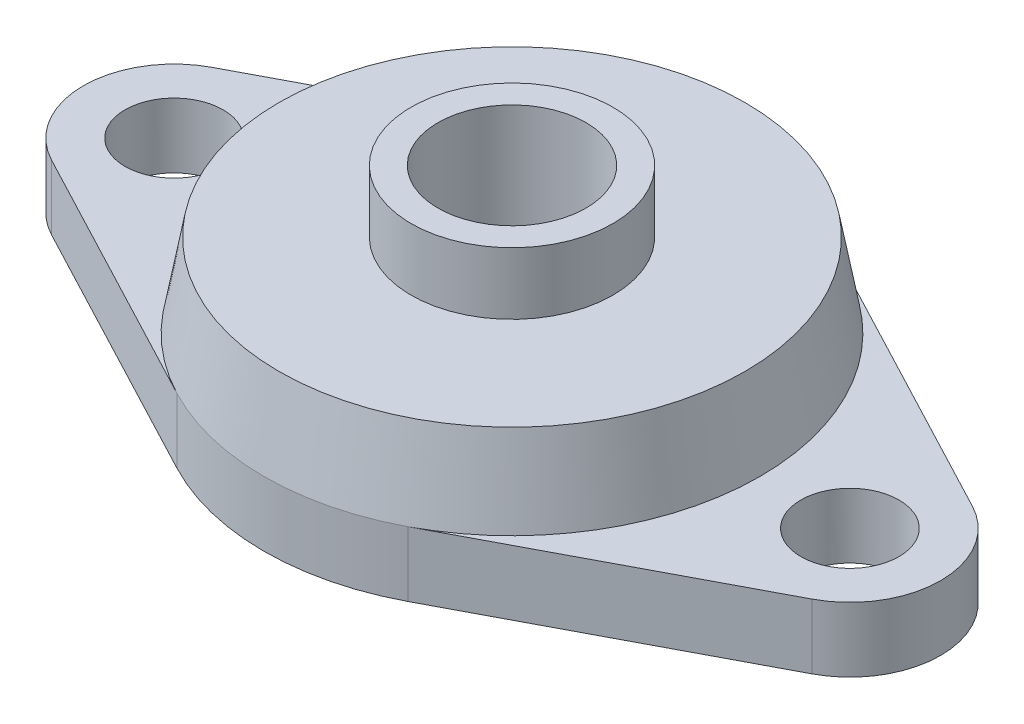
SolidWorks part; units mm, degrees
ref_plane "Front Plane" through (0, 0, 0) normal (0, 0, 1) x (1, 0, 0)
ref_plane "Top Plane" through (0, 0, 0) normal (0, 1, 0) x (1, 0, 0)
ref_plane "Right Plane" through (0, 0, 0) normal (1, 0, 0) x (0, 0, -1)
ref_axis "Axis1" through (0, -0.5675, 0) along (0, 1, 0)
imported_body "Imported1" [suppressed]
imported_body "Imported2" [suppressed]
imported_body "Imported3" [suppressed]
imported_body "Imported4" [suppressed]
sketch "Sketch1" plane through (0, 0, 0) normal (0, 1, 0) x (1, 0, 0)
  line L0 (-23.15, 0) -> (0, 0)
  line L2 (0, 0) -> (0, 13.4)
  line L3 (-23.15, 0) -> (-23.15, 8.4691) construction
  line L8 (-6.2411, 11.8579) -> (-20.5322, 4.3361)
  arc A11 (-20.5322, 4.3361) -> (-23.15, 0) centre (-18.25, 0) ccw
  arc A12 (0, 13.4) -> (-6.2411, 11.8579) centre (0, 0) ccw
  dimension "D3" = 4.9
  dimension "D2" = 23.15
  dimension "D4" = 13.4
extrude "Boss-Extrude1" add sketch "Sketch1" along normal blind 3.5 separate body
mirror "Mirror3" about plane through (0, 3.5, 0) normal (-1, 0, 0) of bodies 105
mirror "Mirror4" about plane through (-23.15, 3.5, 0) normal (0, 0, -1) of bodies 107
sketch "Sketch2" plane through (0, 0, 0) normal (0, 0, 1) x (1, 0, 0)
  line L0 (0, 0) -> (0, 11.35)
  line L2 (0, 11.35) -> (5.45, 11.35)
  line L3 (5.45, 11.35) -> (5.45, 8)
  line L4 (5.45, 8) -> (12.5825, 8)
  line L5 (12.5825, 8) -> (13.4, 3.5)
  line L6 (13.4, 3.5) -> (13.4, 0)
  line L7 (13.4, 0) -> (0, 0)
  dimension "D1" = 11.35
  dimension "D2" = 5.45
  dimension "D3" = 8
  dimension "D4" = 13.4
  dimension "D5" = 3.5
  dimension "D6" = 12.5825
revolve "Revolve1" add sketch "Sketch2" angle 360 about L0
sketch "Sketch3" plane through (0, 0, 0) normal (0, -1, 0) x (1, 0, 0)
  circle A0 centre (0, 0) radius 4
  dimension "D1" = 8
extrude "Cut-Extrude1" cut sketch "Sketch3" against normal through all
hole_wizard "M5 Clearance Hole1" positions "Sketch5" profile "Sketch4" hole size "M5" standard "ANSI Metric" end condition through all
sketch "Sketch5" plane through (0, 0, 0) normal (0, -1, 0) x (-1, 0, 0)
  line L0 (18.25, 0) -> (-18.25, 0) construction
  point P0 (18.25, 0)
  point P2 (-18.25, 0)
  dimension "D1" = 36.5
sketch "Sketch4" plane through (-18.25, 0, 0) normal (1, 0, 0) x (0, 0, -1)
  line L0 (0, 0) -> (0, 11.35)
  line L1 (0, 11.35) -> (2.65, 11.35)
  line L2 (2.65, 11.35) -> (2.65, 0)
  line L5 (2.65, 0) -> (0, 0)
  line L11 (0, -6.35) -> (0, 107.95) construction
  dimension "Thru Hole Dia." = 5.3
  dimension "Thru Hole Depth" = 11.35
